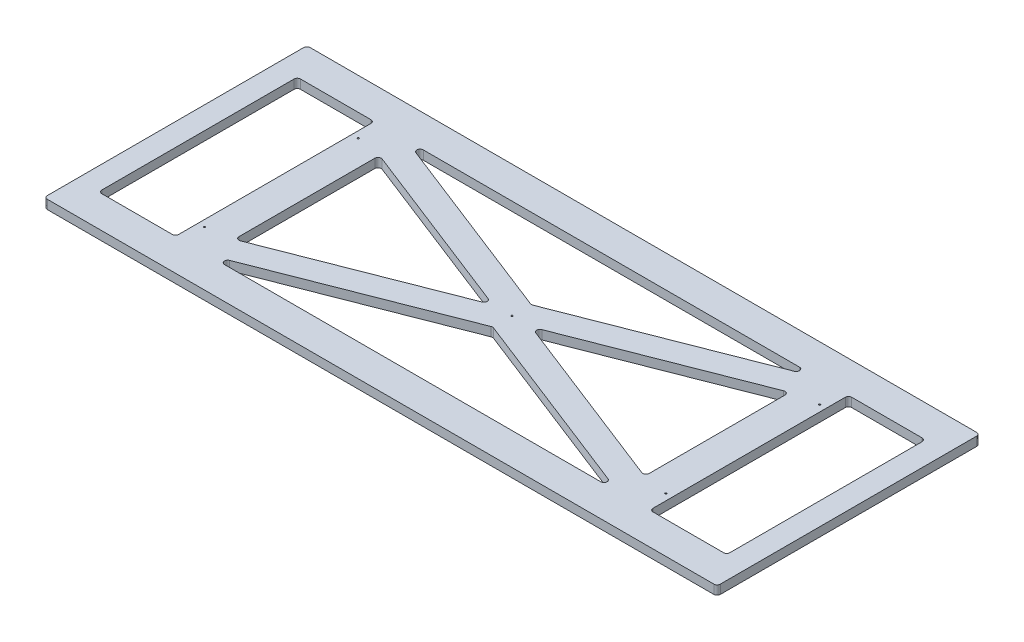
SolidWorks part; units mm, degrees
ref_plane "Front Plane" through (0, 0, 0) normal (0, 0, 1) x (1, 0, 0)
ref_plane "Top Plane" through (0, 0, 0) normal (0, 1, 0) x (1, 0, 0)
ref_plane "Right Plane" through (0, 0, 0) normal (1, 0, 0) x (0, 0, -1)
sketch "Sketch1" plane through (0, 0, 0) normal (0, 1, 0) x (1, 0, 0)
  line L1 (-666.75, 260.35) -> (666.75, 260.35)
  line L2 (-666.75, 260.35) -> (-666.75, -260.35)
  line L3 (-666.75, -260.35) -> (666.75, -260.35)
  line L4 (666.75, 260.35) -> (666.75, -260.35)
  line L5 (-666.75, 260.35) -> (666.75, -260.35) construction
  line L6 (-666.75, -260.35) -> (666.75, 260.35) construction
  point P0 (0, 0)
  dimension "D1" = 520.7
  dimension "D2" = 1333.5
extrude "Boss-Extrude1" add sketch "Sketch1" along normal blind 17.78
fillet "Fillet1" radius 6.35 4 edges at (-666.75, 8.89, 260.35) (-666.75, 8.89, -260.35) (666.75, 8.89, -260.35) (666.75, 8.89, 260.35)
hole_wizard "1/8 (0.125) Diameter Hole1" positions "Sketch3" profile "Sketch4" hole size "1/8" standard "ANSI Inch" end condition through all
sketch "Sketch3" plane through (0, 17.78, 0) normal (0, 1, 0) x (1, 0, 0)
  line L1 (-457.2, -152.4) -> (457.2, -152.4) construction
  line L2 (-457.2, -152.4) -> (-457.2, 152.4) construction
  line L3 (-457.2, 152.4) -> (457.2, 152.4) construction
  line L4 (457.2, -152.4) -> (457.2, 152.4) construction
  line L5 (-457.2, -152.4) -> (457.2, 152.4) construction
  line L6 (-457.2, 152.4) -> (457.2, -152.4) construction
  point P0 (0, 0)
  point P1 (457.2, 152.4)
  point P32 (-457.2, -152.4)
  point P33 (-457.2, 152.4)
  point P34 (457.2, -152.4)
  dimension "D1" = 914.4
  dimension "D2" = 304.8
sketch "Sketch4" plane through (0, 17.78, 0) normal (1, 0, 0) x (0, 0, 1)
  line L0 (0, 0) -> (0, 17.78)
  line L1 (0, 17.78) -> (1.5875, 17.78)
  line L2 (1.5875, 17.78) -> (1.5875, 0)
  line L5 (1.5875, 0) -> (0, 0)
  line L11 (0, -6.35) -> (0, 107.95) construction
  dimension "Thru Hole Dia." = 3.175
  dimension "Thru Hole Depth" = 17.78
sketch "Sketch2" plane through (0, 17.78, 0) normal (0, 1, 0) x (1, 0, 0)
  line L1 (-635, -330.2) -> (635, -330.2)
  line L2 (-635, -330.2) -> (-635, 330.2)
  line L3 (-635, 330.2) -> (635, 330.2)
  line L4 (635, -330.2) -> (635, 330.2)
  line L5 (-635, -330.2) -> (635, 330.2) construction
  line L6 (-635, 330.2) -> (635, -330.2) construction
  point P0 (0, 0)
  dimension "D1" = 660.4
  dimension "D2" = 1270
extrude "Boss-Extrude2" [suppressed] add sketch "Sketch2" along normal blind 9.525
sketch "Sketch5" plane through (0, 17.78, 0) normal (0, 1, 0) x (1, 0, 0)
  line L0 (-406.4, 196.85) -> (406.4, 196.85)
  line L1 (660.4, 260.35) -> (-660.4, 260.35) construction
  line L2 (0, 38.1) -> (-406.4, 196.85)
  line L3 (406.4, 196.85) -> (0, 38.1)
  line L4 (0, 260.35) -> (0, -260.35) construction
  line L5 (-660.4, -260.35) -> (660.4, -260.35) construction
  line L6 (-666.75, 0) -> (666.75, 0) construction
  line L7 (-666.75, 254) -> (-666.75, -254) construction
  line L8 (666.75, -254) -> (666.75, 254) construction
  line L9 (0, -38.1) -> (-406.4, -196.85)
  line L10 (-406.4, -196.85) -> (406.4, -196.85)
  line L11 (406.4, -196.85) -> (0, -38.1)
  line L12 (406.4, 143.8672) -> (406.4, -143.8672)
  line L13 (406.4, -143.8672) -> (38.1, 0)
  line L14 (406.4, 143.8672) -> (38.1, 0)
  line L15 (-406.4, 143.8672) -> (-38.1, 0)
  line L16 (-406.4, 143.8672) -> (-406.4, -143.8672)
  line L17 (-406.4, -143.8672) -> (-38.1, 0)
  line L18 (622.3, -196.85) -> (469.9, -196.85)
  line L19 (-622.3, -196.85) -> (-469.9, -196.85)
  line L20 (-622.3, -196.85) -> (-622.3, 196.85)
  line L21 (-622.3, 196.85) -> (-469.9, 196.85)
  line L22 (-469.9, -196.85) -> (-469.9, 196.85)
  line L23 (-622.3, -196.85) -> (-469.9, 196.85) construction
  line L24 (-622.3, 196.85) -> (-469.9, -196.85) construction
  line L25 (622.3, -196.85) -> (622.3, 196.85)
  line L26 (622.3, 196.85) -> (469.9, 196.85)
  line L27 (469.9, -196.85) -> (469.9, 196.85)
  circle A0 centre (0, 0) radius 38.1 construction
  point P3 (0, 196.85)
  point P30 (-546.1, 0)
  dimension "D2" = 76.2
  dimension "D4" = 152.4
  dimension "D1" = 63.5
  dimension "D3" = 812.8
  dimension "D5" = 44.45
extrude "Cut-Extrude1" cut sketch "Sketch5" against normal through all
fillet "Fillet2" radius 6.35 20 edges at (469.9, 8.89, -196.85) (469.9, 8.89, 196.85) (622.3, 8.89, 196.85) (406.4, 8.89, 143.8672) (406.4, 8.89, 196.85) (622.3, 8.89, -196.85) (406.4, 8.89, -143.8672) (406.4, 8.89, -196.85) (38.1, 8.89, 0) (0, 8.89, 38.1) (0, 8.89, -38.1) (-38.1, 8.89, 0) (-406.4, 8.89, 196.85) (-406.4, 8.89, -196.85) (-406.4, 8.89, -143.8672) (-406.4, 8.89, 143.8672) (-622.3, 8.89, 196.85) (-469.9, 8.89, 196.85) (-469.9, 8.89, -196.85) (-622.3, 8.89, -196.85)
